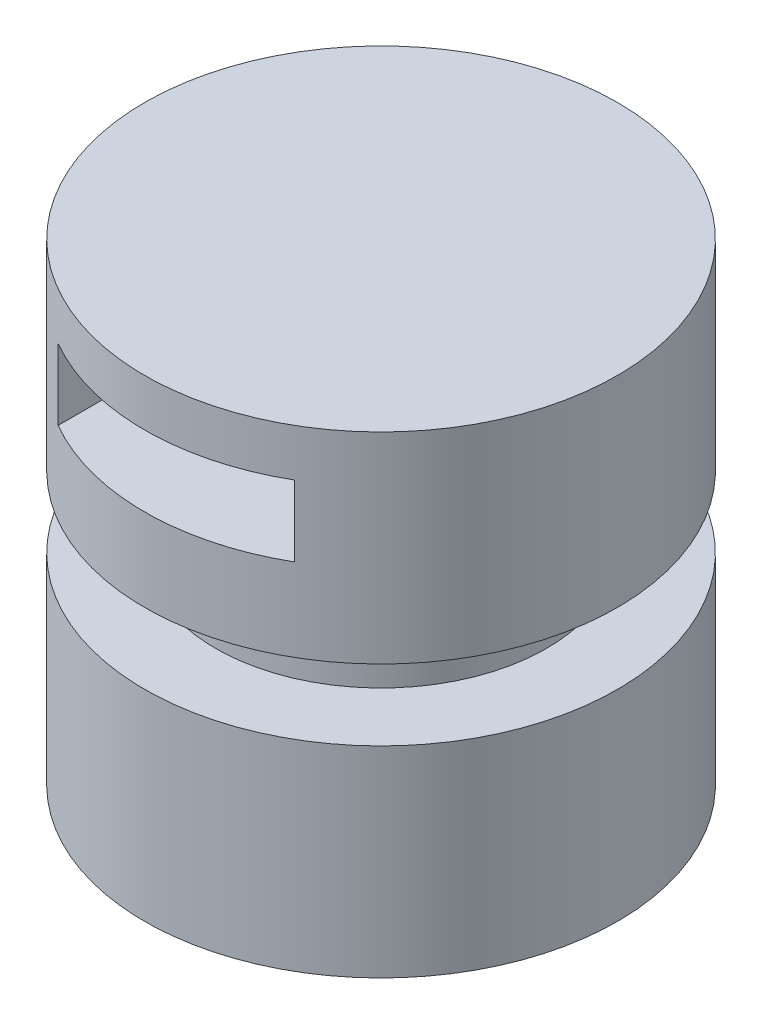
SolidWorks part; units mm, degrees
ref_plane "Front Plane" through (0, 0, 0) normal (0, 0, 1) x (1, 0, 0)
ref_plane "Top Plane" through (0, 0, 0) normal (0, 1, 0) x (1, 0, 0)
ref_plane "Right Plane" through (0, 0, 0) normal (1, 0, 0) x (0, 0, -1)
sketch "Sketch2" plane through (0, 0, 0) normal (0, 0, 1) x (1, 0, 0)
  line L1 (0, 0) -> (2540, 0)
  line L2 (0, 0) -> (0, 5080)
  line L3 (0, 5080) -> (2540, 5080)
  line L4 (2540, 0) -> (2540, 5080)
  dimension "D1" = 2540
  dimension "D2" = 5080
revolve "Revolve2" add sketch "Sketch2" angle 360 about L2
sketch "Sketch3" plane through (0, 0, 0) normal (1, 0, 0) x (0, 0, -1)
  line L0 (0, 0) -> (0, 5080) construction
  line L1 (2540, 2921) -> (1778, 2921)
  line L2 (2540, 2921) -> (2540, 2159)
  line L3 (2540, 2159) -> (1778, 2159)
  line L4 (1778, 2921) -> (1778, 2159)
  line L5 (2540, 5080) -> (-2540, 5080) construction
  line L6 (2540, 0) -> (2540, 5080) construction
  line L7 (0, 2540) -> (2540, 2540) construction
  line L8 (1778, 2540) -> (2540, 2540) construction
  point P16 (0, 0)
  dimension "D1" = 762
  dimension "D2" = 2540
revolve "Revolve3" add sketch "Sketch3" angle 360 about L0 other way angle 360
revolve "Cut-Revolve1" cut sketch "Sketch3<2>" angle 360 about L0
sketch "Sketch3<2>" plane through (0, 0, 0) normal (1, 0, 0) x (0, 0, -1) same geometry as "Sketch3"
sketch "Sketch4" plane through (0, 0, 0) normal (0, 0, 1) x (1, 0, 0)
  line L0 (2540, 5080) -> (-2540, 5080) construction
  line L1 (-1270, 4572) -> (1270, 4572)
  line L2 (-1270, 4572) -> (-1270, 3810)
  line L3 (-1270, 3810) -> (1270, 3810)
  line L4 (1270, 4572) -> (1270, 3810)
  line L5 (0, 3810) -> (0, 5080) construction
  dimension "D1" = 2540
  dimension "D2" = 762
  dimension "D3" = 508
extrude "Cut-Extrude1" cut sketch "Sketch4" against normal through all both and the other way through all
